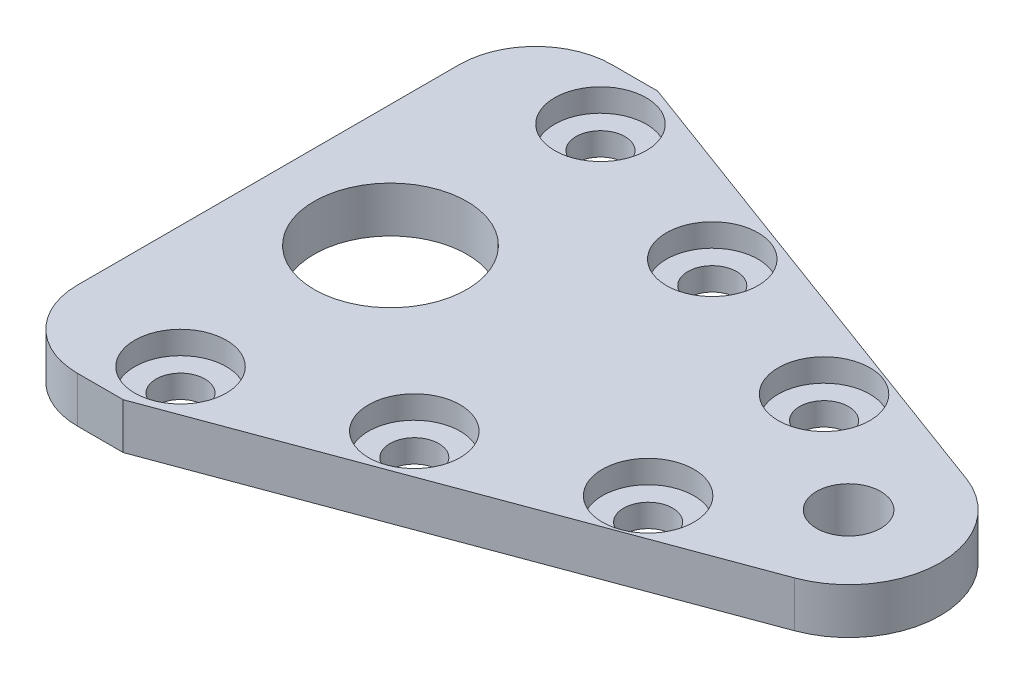
SolidWorks part; units mm, degrees
ref_plane "Front Plane" through (0, 0, 0) normal (0, 0, 1) x (1, 0, 0)
ref_plane "Top Plane" through (0, 0, 0) normal (0, 1, 0) x (1, 0, 0)
ref_plane "Right Plane" through (0, 0, 0) normal (1, 0, 0) x (0, 0, -1)
sketch "Sketch1" plane through (0, 0, 0) normal (0, 1, 0) x (1, 0, 0)
  line L0 (0, 0) -> (30, 0) construction
  line L1 (-30, -17.5) -> (30, -17.5)
  line L2 (-30, -17.5) -> (-30, 17.5)
  line L3 (-30, 17.5) -> (30, 17.5)
  line L4 (30, -17.5) -> (30, 17.5)
  line L5 (-30, -17.5) -> (30, 17.5) construction
  line L6 (-30, 17.5) -> (30, -17.5) construction
  line L7 (0, 17.5) -> (0, -17.5) construction
  line L8 (0, 17.5) -> (32.0824, 5.627)
  line L9 (0, -17.5) -> (32.0824, -5.627)
  line L10 (-8, 17.5) -> (-8, -17.5)
  circle A0 centre (0, 0) radius 5
  circle A1 centre (30, 0) radius 2.1
  circle A2 centre (30, 0) radius 6
  point P0 (0, 0)
  dimension "D1" = 10
  dimension "D5" = 4.2
  dimension "D6" = 12
  dimension "D2" = 60
  dimension "D3" = 35
  dimension "D4" = 30
  dimension "D7" = 8
extrude "Boss-Extrude1" add sketch "Sketch1" along normal blind 3 contours A2 L4 L9 | L4 A2 A1 | A2 L8 L4 | A2 L4 L8 L3 L2 L1 L9 A0 | L4 A2 A1 region at (7.4447, 0, 0) region at (30.5272, 0, 6.0827) region at (27.2225, 0, 0) region at (32.7775, 0, 0) region at (30.5272, 0, -6.0827)
sketch "Sketch3" plane through (0, 3, 0) normal (0, 1, 0) x (1, 0, 0)
  line L0 (0, 13.75) -> (0, -13.75) construction
  line L1 (0, -13.75) -> (39.2829, 0) construction
  line L2 (39.2829, 0) -> (0, 13.75) construction
  line L3 (0, 0) -> (39.2829, 0) construction
  line L4 (-8, 17.5) -> (-8, -17.5) construction
  line L7 (0, 17.5) -> (0, 13.75) construction
  line L8 (0, 13.75) -> (0, -13.75) construction
  line L9 (0, -13.75) -> (0, -17.5) construction
  circle A0 centre (0, 13.75) radius 1.6
  circle A1 centre (11.3154, 9.7549) radius 1.6
  circle A2 centre (22.6309, 5.7598) radius 1.6
  circle A3 centre (22.6309, -5.7598) radius 1.6
  circle A4 centre (0, -13.75) radius 1.6
  circle A5 centre (11.3154, -9.7549) radius 1.6
  dimension "D2" = 3.2
  dimension "D1" = 3.75
  dimension "D4" = 3.75
  dimension "D3" = 3
extrude "Cut-Extrude1" cut sketch "Sketch3" against normal blind 10
fillet "Fillet1" radius 5 2 edges at (-8, 1.5, 17.5) (-8, 1.5, -17.5)
sketch "Sketch4" plane through (0, 3, 0) normal (0, 1, 0) x (1, 0, 0)
  circle A0 centre (0, 13.75) radius 3
  circle A1 centre (11.3154, 9.7549) radius 3
  circle A2 centre (22.6309, 5.7598) radius 3
  circle A3 centre (22.6309, -5.7598) radius 3
  circle A4 centre (11.3154, -9.7549) radius 3
  circle A5 centre (0, -13.75) radius 3
  dimension "D1" = 6
extrude "Cut-Extrude2" cut sketch "Sketch4" against normal blind 1.5
